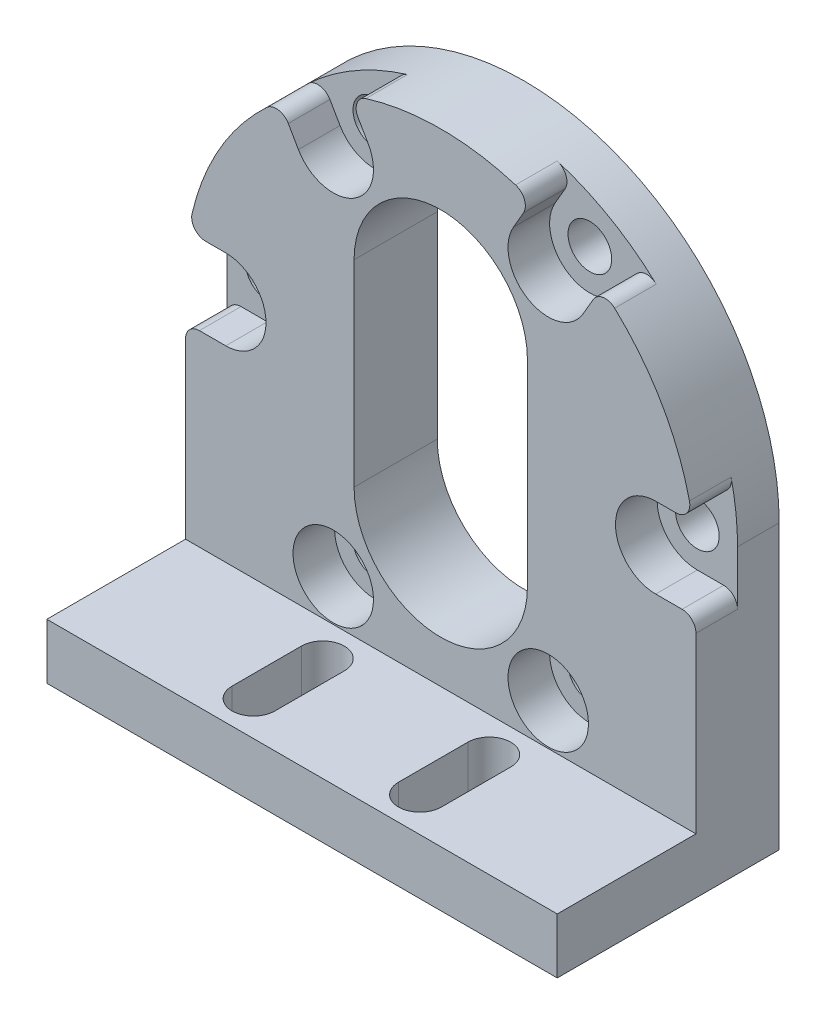
SolidWorks part; units mm, degrees
ref_plane "Front Plane" through (0, 0, 0) normal (0, 0, 1) x (1, 0, 0)
ref_plane "Top Plane" through (0, 0, 0) normal (0, 1, 0) x (1, 0, 0)
ref_plane "Right Plane" through (0, 0, 0) normal (1, 0, 0) x (0, 0, -1)
sketch "Sketch1" plane through (0, 0, 0) normal (0, 0, 1) x (1, 0, 0)
  line L0 (0, -7.1) -> (0, 7.1) construction
  line L1 (-6.25, -7.1) -> (-6.25, 7.1)
  line L2 (6.25, -7.1) -> (6.25, 7.1)
  line L3 (-18.4, 0) -> (-18.4, -19)
  line L4 (-18.4, -19) -> (18.4, -19)
  line L5 (18.4, -19) -> (18.4, 0)
  circle A0 centre (0, 0) radius 18.4
  arc A1 (-6.25, -7.1) -> (6.25, -7.1) centre (0, -7.1) ccw
  arc A2 (6.25, 7.1) -> (-6.25, 7.1) centre (0, 7.1) ccw
  circle A8 centre (-15.5, 0) radius 1.575
  circle A14 centre (-7.75, 13.4234) radius 1.575
  circle A15 centre (7.75, 13.4234) radius 1.575
  circle A16 centre (15.5, 0) radius 1.575
  circle A17 centre (7.75, -13.4234) radius 1.575
  circle A18 centre (-7.75, -13.4234) radius 1.575
  point P5 (0, 0)
  point P28 (0, 0)
  point P30 (0, 0)
  dimension "D1" = 36.8
  dimension "D3" = 6.25
  dimension "D5" = 15.5
  dimension "D6" = 3.15
  dimension "D2" = 7.1
  dimension "D4" = 19
extrude "Boss-Extrude1" add sketch "Sketch1" along normal blind 6 contours A0 A8 A2 L2 A1 L1 | A0 L3 L4 L5 region at (0, -18.8142, 0) region at (0, 17.8796, 0)
ref_axis "Axis2" through (0, 0, 6) along (0, 0, -1)
sketch "Sketch2" plane through (0, 0, 6) normal (0, 0, 1) x (1, 0, 0)
  line L0 (-15.5, 2.9) -> (-19.6935, 2.9)
  line L1 (-15.5, -2.9) -> (-19.6935, -2.9)
  line L3 (-5.2385, 14.8734) -> (-7.3353, 18.505)
  line L4 (-10.2615, 11.9734) -> (-12.3582, 15.605)
  line L5 (10.2615, 11.9734) -> (12.3582, 15.605)
  line L6 (5.2385, 14.8734) -> (7.3353, 18.505)
  line L7 (15.5, -2.9) -> (19.6935, -2.9)
  line L8 (15.5, 2.9) -> (19.6935, 2.9)
  line L9 (0, 0) -> (-15.5, 0) construction
  line L10 (0, 0) -> (-7.75, 13.4234) construction
  line L11 (5.2385, -14.8734) -> (7.3353, -18.505)
  line L12 (10.2615, -11.9734) -> (12.3582, -15.605)
  line L13 (-10.2615, -11.9734) -> (-12.3582, -15.605)
  line L14 (-5.2385, -14.8734) -> (-7.3353, -18.505)
  circle A0 centre (-15.5, 0) radius 2.9
  circle A12 centre (-7.75, 13.4234) radius 2.9
  circle A13 centre (7.75, 13.4234) radius 2.9
  circle A14 centre (15.5, 0) radius 2.9
  circle A15 centre (7.75, -13.4234) radius 2.9
  circle A16 centre (-7.75, -13.4234) radius 2.9
  circle M6 centre (-15.5, 0) radius 1.575
  arc M11 (18.4, 0) -> (-18.4, 0) centre (0, 0) ccw
  line M12 (-18.4, 0) -> (-18.4, -19)
  line M14 (18.4, -19) -> (18.4, 0)
  circle M42 centre (7.75, -13.4234) radius 1.575
  circle M43 centre (15.5, 0) radius 1.575
  circle M44 centre (7.75, 13.4234) radius 1.575
  circle M45 centre (-7.75, 13.4234) radius 1.575
  dimension "D1" = 5.8
  dimension "D2" = 60
  dimension "D3" = 6
extrude "Cut-Extrude3" cut sketch "Sketch2" against normal blind 3 contours A0 M6 | A0 L0 M11 | A0 L1 M12 | A12 L3 M11 | A12 L4 M11 | A12 M45 | A13 L6 M11 | A13 M44 | A13 L5 M11 | A14 L8 M11 | A14 M43 | A14 L7 M14 region at (-17.6712, 2.2629, 6) region at (17.6712, 2.2629, 6) region at (6.8758, 16.4351, 6) region at (-10.7953, 14.1722, 6) region at (-13.5074, 1.9926, 6) region at (-17.7522, -2.2522, 6) region at (-10.472, 14.1527, 6) region at (-6.8758, 16.4351, 6) region at (7.0207, 16.1453, 6) region at (10.7953, 14.1722, 6) region at (17.4926, 1.9926, 6) region at (17.7522, -2.2522, 6)
fillet "Fillet1" [suppressed] radius 1
extrude "Cut-Extrude4" cut sketch "Sketch2<3>" against normal blind 3 contours A15 M42 | A16 region at (8.4793, -16.1453, 6)
sketch "Sketch2<3>" plane through (0, 0, 6) normal (0, 0, 1) x (1, 0, 0) same geometry as "Sketch2"
sketch "Sketch3" plane through (0, 0, 0) normal (0, 0, 1) x (1, 0, 0)
  line L0 (18.4, -19) -> (18.4, 0) construction
  line L1 (-18.4, -16.4234) -> (18.4, -16.4234)
  line L2 (-18.4, -16.4234) -> (-18.4, -20.4234)
  line L3 (-18.4, -20.4234) -> (18.4, -20.4234)
  line L4 (18.4, -16.4234) -> (18.4, -20.4234)
  line L5 (-18.4, 0) -> (-18.4, -19) construction
  circle A0 centre (-7.75, -13.4234) radius 2.9 construction
  dimension "D2" = 3
  dimension "D1" = 4
extrude "Boss-Extrude2" add sketch "Sketch3" along normal offset from surface (16 mm away) 10 up to face at (10.65, -13.4234, 6) offset beyond the face yes
sketch "Sketch4" plane through (0, -16.4234, 0) normal (0, 1, 0) x (1, 0, 0)
  line L0 (0, -16) -> (0, -6) construction
  line L1 (18.4, -16) -> (-18.4, -16) construction
  line L2 (0, -6) -> (-15.5, -6) construction
  line L3 (0, -6) -> (0, 0) construction
  line L4 (-6, -8.5) -> (-6, -13.5) construction
  line L5 (-4.45, -8.5) -> (-4.45, -13.5)
  line L6 (-7.55, -8.5) -> (-7.55, -13.5)
  line L7 (6, -8.5) -> (6, -13.5) construction
  line L8 (4.45, -8.5) -> (4.45, -13.5)
  line L9 (7.55, -8.5) -> (7.55, -13.5)
  arc A0 (-4.45, -8.5) -> (-7.55, -8.5) centre (-6, -8.5) ccw
  arc A1 (-7.55, -13.5) -> (-4.45, -13.5) centre (-6, -13.5) ccw
  arc A2 (4.45, -8.5) -> (7.55, -8.5) centre (6, -8.5) cw
  arc A3 (7.55, -13.5) -> (4.45, -13.5) centre (6, -13.5) cw
  point P10 (-6, -11)
  point P15 (0, 0)
  point P16 (0, -11)
  point P19 (6, -11)
  dimension "D3" = 1.55
  dimension "D1" = 5
  dimension "D2" = 6
extrude "Cut-Extrude5" cut sketch "Sketch4" against normal blind 10
fillet "Fillet2" radius 1 8 edges at (18.4, -2.9, 4.5) (18.17, 2.9, 4.5) (11.5965, 14.2857, 4.5) (6.5735, 17.1857, 4.5) (-6.5735, 17.1857, 4.5) (-11.5965, 14.2857, 4.5) (-18.4, -2.9, 4.5) (-18.17, 2.9, 4.5)
